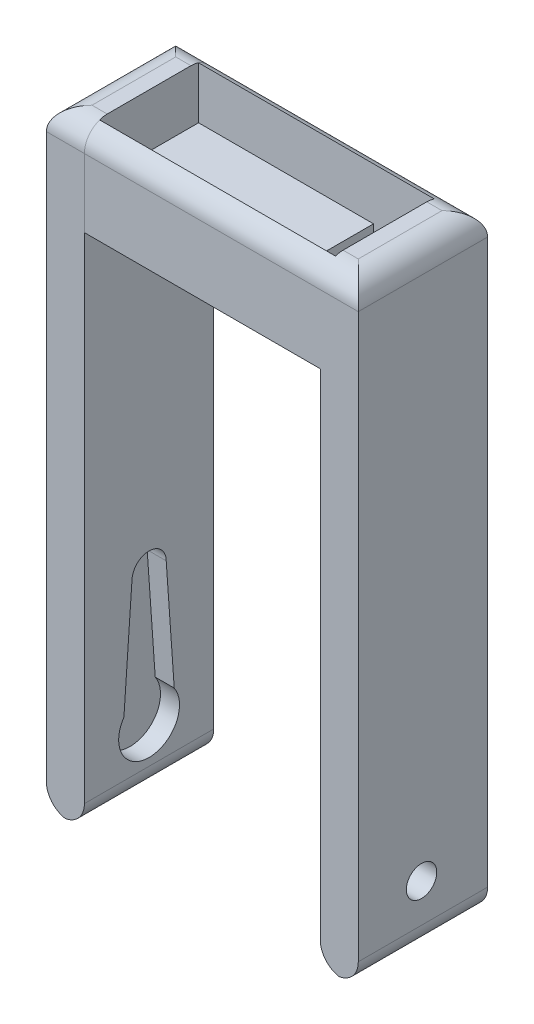
SolidWorks part; units mm, degrees
ref_plane "Front Plane" through (0, 0, 0) normal (0, 0, 1) x (1, 0, 0)
ref_plane "Top Plane" through (0, 0, 0) normal (0, 1, 0) x (1, 0, 0)
ref_plane "Right Plane" through (0, 0, 0) normal (1, 0, 0) x (0, 0, -1)
sketch "Sketch1" plane through (0, 0, 0) normal (0, 1, 0) x (1, 0, 0)
  line L1 (0, 0) -> (5, 0)
  line L2 (0, 0) -> (0, -17)
  line L3 (0, -17) -> (5, -17)
  line L4 (5, 0) -> (5, -17)
  line L5 (36, 0) -> (41, 0)
  line L6 (36, 0) -> (36, -17)
  line L7 (36, -17) -> (41, -17)
  line L8 (41, 0) -> (41, -17)
  dimension "D1" = 5
  dimension "D2" = 5
  dimension "D3" = 31
  dimension "D4" = 17
  dimension "D5" = 17
extrude "Boss-Extrude1" add sketch "Sketch1" along normal blind 80
sketch "Sketch2" plane through (5, 0, 0) normal (1, 0, 0) x (0, 0, -1)
  line L0 (-11.8072, 10.25) -> (-10.75, 25.2678)
  line L1 (-11.8072, 10.25) -> (-11.8072, 5.75)
  line L2 (-17, 0) -> (0, 0) construction
  line L3 (-5.1928, 5.75) -> (-5.1928, 10.25)
  line L4 (-5.1928, 10.25) -> (-6.25, 25.2678)
  circle A0 centre (-8.5, 8) radius 4
  arc A1 (-10.75, 25.2678) -> (-6.25, 25.2678) centre (-8.5, 25.2678) cw
  point P6 (-8.5, 0)
  dimension "D1" = 8
  dimension "D3" = 2.25
  dimension "D2" = 4.5
  dimension "D4" = 4.5
  dimension "D5" = 8
extrude "Cut-Extrude1" cut sketch "Sketch2" against normal blind 2.5 contours A1 L0 A0 L4 | L3 A0 L1 | L1 A0 | L3 A0 region at (5, 8, 8.5) region at (5, 18.7534, 8.5) region at (5, 8, 12.0865) region at (5, 8, 4.9135)
sketch "Sketch4" plane through (36, 0, 0) normal (-1, 0, 0) x (0, 0, 1)
  line L0 (0, 80) -> (0, 0) construction
  line L1 (2, 73) -> (15, 73)
  line L2 (0, 72) -> (0, 68)
  line L3 (0, 68) -> (17, 68)
  line L4 (17, 72) -> (17, 68)
  line L5 (17, 80) -> (17, 0) construction
  line L6 (0, 80) -> (17, 80) construction
  line L8 (0, 80) -> (2, 80)
  line L9 (0, 80) -> (0, 72)
  line L11 (2, 80) -> (2, 73)
  line L12 (17, 80) -> (15, 80)
  line L13 (17, 80) -> (17, 72)
  line L15 (15, 80) -> (15, 73)
  dimension "D1" = 7
  dimension "D2" = 5
  dimension "D3" = 13
  dimension "D4" = 2
extrude "Boss-Extrude2" add sketch "Sketch4" along normal up to next
sketch "Sketch5" plane through (0, 73, 0) normal (0, 1, 0) x (1, 0, 0)
  line L0 (5, -15) -> (36, -15) construction
  line L1 (31, -15) -> (28, -15)
  line L2 (31, -15) -> (31, -2)
  line L3 (31, -2) -> (28, -2)
  line L4 (28, -15) -> (28, -2)
  line L5 (5, -2) -> (36, -2) construction
  line L6 (36, -15) -> (36, -2) construction
  dimension "D1" = 5
  dimension "D2" = 3
extrude "Cut-Extrude2" cut sketch "Sketch5" against normal up to next (5 mm away)
fillet "Fillet1" radius 3 5 edges at (36, 0, 8.5) (41, 0, 8.5) (41, 80, 8.5) (23, 80, 17) (23, 80, 0)
fillet "Fillet2" radius 3 5 edges at (0, 0, 8.5) (5, 0, 8.5) (2.5, 80, 17) (0, 80, 8.5) (2.5, 80, 0)
sketch "Sketch6" plane through (36, 0, 0) normal (-1, 0, 0) x (0, 0, 1)
  line L0 (0, 0.042) -> (17, 0.042) construction
  circle A0 centre (8.6864, 8.042) radius 2
  point P2 (8.5, 0.042)
  dimension "D2" = 4
  dimension "D1" = 8
extrude "Cut-Extrude3" cut sketch "Sketch6" against normal through all
